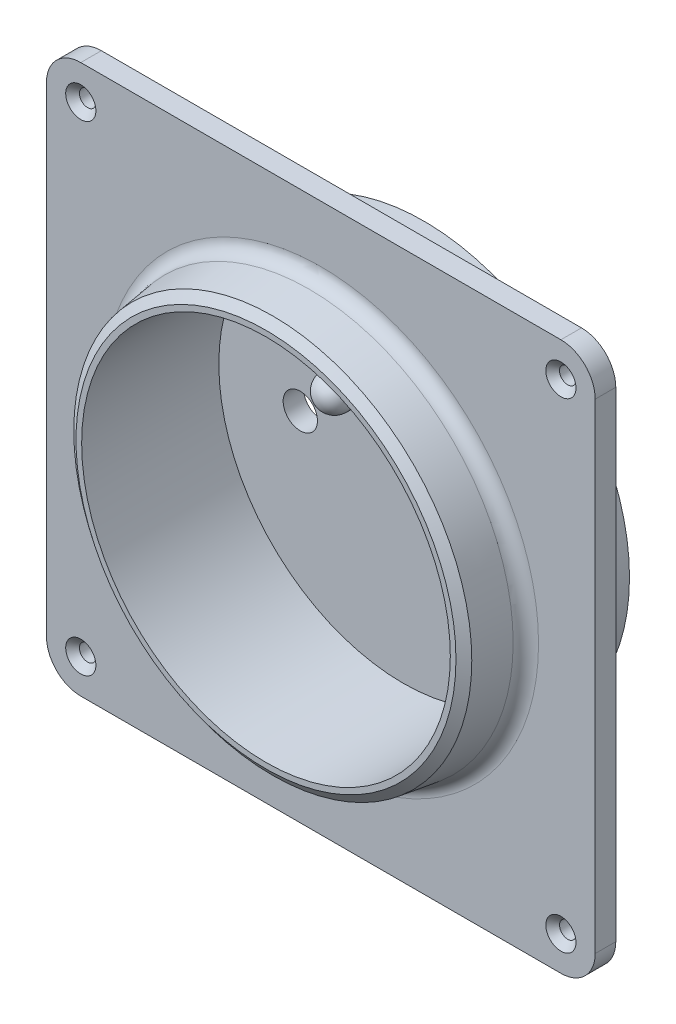
SolidWorks part; units mm, degrees
ref_plane "Plan de face" through (0, 0, 0) normal (0, 0, 1) x (1, 0, 0)
ref_plane "Plan de dessus" through (0, 0, 0) normal (0, 1, 0) x (1, 0, 0)
ref_plane "Plan de droite" through (0, 0, 0) normal (1, 0, 0) x (0, 0, -1)
sketch "Profil Base" plane through (0, 0, 0) normal (0, 0, 1) x (1, 0, 0)
  line L1 (-40, 40) -> (40, 40)
  line L2 (-40, 40) -> (-40, -40)
  line L3 (-40, -40) -> (40, -40)
  line L4 (40, 40) -> (40, -40)
  line L5 (-40, 40) -> (40, -40) construction
  line L6 (-40, -40) -> (40, 40) construction
  point P0 (0, 0)
  dimension "D1" = 80
extrude "Boss.-Extru.1" add sketch "Profil Base" along normal mid plane 3
fillet "Congé1" radius 5 4 edges at (40, -40, 0) (-40, -40, 0) (-40, 40, 0) (40, 40, 0)
sketch "Esquisse2" plane through (0, 0, 1.5) normal (0, 0, 1) x (1, 0, 0)
  circle A0 centre (0, 0) radius 30
  dimension "D1" = 60
extrude "Boss.-Extru.2" add sketch "Esquisse2" along normal blind 8 draft 8 and the other way blind 15
sketch "Esquisse4" plane through (0, 0, 9.5) normal (0, 0, 1) x (1, 0, 0)
  circle A2 centre (0, 0) radius 26.8757
  circle A3 centre (0, 0) radius 26.8757
  dimension "D1" = 2
extrude "Enlèv. mat.-Extru.1" cut sketch "Esquisse4" against normal offset from surface (20 mm away) 3 up to face at (30, 0, -13.5)
hole_wizard "Diamètre du perçage Ø0.15 (5)1" positions "Esquisse7" profile "Esquisse6" hole size "Ø0.15" standard "Ansi Metric" end condition through all
sketch "Esquisse7" plane through (0, 0, -10.5) normal (0, 0, 1) x (1, 0, 0)
  line L0 (0, 0) -> (0, 26.8757) construction
  circle A0 centre (0, 0) radius 26.8757 construction
  point P0 (-15, 0)
  point P2 (15, 0)
  dimension "D1" = 30
  dimension "D2" = 15
sketch "Esquisse6" plane through (-15, 0, -10.5) normal (1, 0, 0) x (0, -1, 0)
  line L0 (0, 0) -> (0, 3)
  line L1 (0, 3) -> (2.5, 3)
  line L2 (2.5, 3) -> (2.5, 0)
  line L5 (2.5, 0) -> (0, 0)
  line L11 (0, -6.35) -> (0, 107.95) construction
  dimension "Diamètre du perçage jusqu'au prochain" = 5
  dimension "Profondeur du perçage jusqu'au prochain" = 3
sketch "Esquisse8" plane through (0, 0, -10.5) normal (0, 0, 1) x (1, 0, 0)
  circle A0 centre (0, 15) radius 2.5
  dimension "D1" = 5
  dimension "D2" = 15
extrude "Boss.-Extru.3" add sketch "Esquisse8" along normal blind 10
sketch "Esquisse9" plane through (0, 0, -0.5) normal (0, 0, 1) x (1, 0, 0)
  line L0 (0, 17.5) -> (0, 12.5)
  circle A0 centre (0, 15) radius 2.5 construction
  arc A1 (0, 12.5) -> (0, 17.5) centre (0, 15) ccw
revolve "Révolution1" add sketch "Esquisse9" angle 180 about L0
chamfer "Chanfrein1" distance 1 angle 45 1 edges at (28.8757, 0, 9.5) first distance on face at (28.8757, 0, 9.5)
fillet "Congé2" radius 2 2 edges at (30, 0, -1.5) (30, 0, 1.5)
hole_wizard "Fraisage pour vis à tête fraisée M21" positions "Esquisse10" profile "Esquisse11" countersink size "M2" standard "Ansi Metric" end condition through all
sketch "Esquisse10" plane through (0, 0, 1.5) normal (0, 0, 1) x (1, 0, 0)
  point P0 (-35, 35)
  point P3 (35, 35)
  point P6 (-35, -35)
  point P9 (35, -35)
sketch "Esquisse11" plane through (-35, 35, 1.5) normal (1, 0, 0) x (0, -1, 0)
  line L0 (0, 0) -> (0, 15)
  line L1 (0, 15) -> (1.2, 15)
  line L2 (1.2, 15) -> (1.2, 1)
  line L3 (1.2, 1) -> (2.2, 0)
  line L5 (2.2, 0) -> (0, 0)
  line L6 (-1.2, 1) -> (-2.2, 0) construction
  line L11 (0, -6.35) -> (0, 107.95) construction
  dimension "Diamètre du perçage jusqu'au prochain" = 2.4
  dimension "Profondeur du perçage jusqu'au prochain" = 15
  dimension "Diamètre du fraisage entrant" = 4.4
  dimension "Angle du fraisage entrant" = 90
